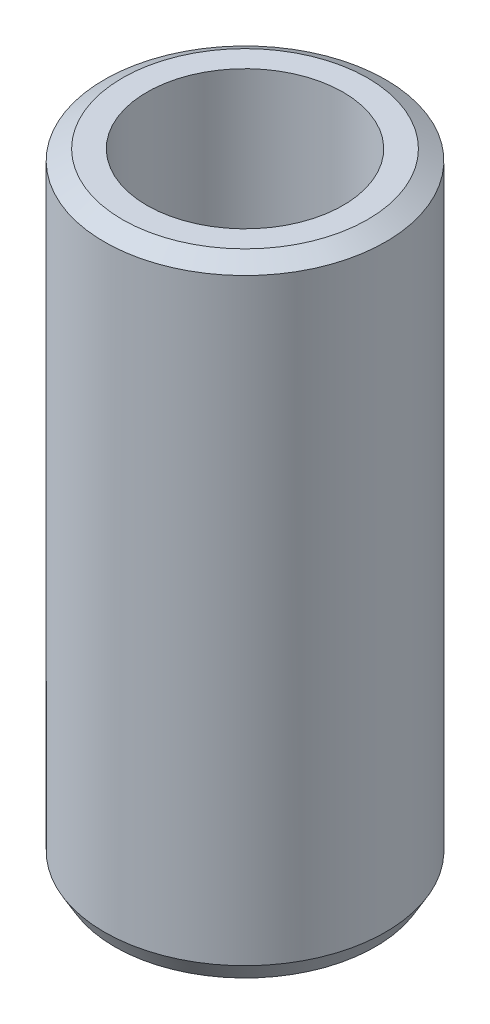
SolidWorks part; units mm, degrees
ref_plane "Front Plane" through (0, 0, 0) normal (0, 0, 1) x (1, 0, 0)
ref_plane "Top Plane" through (0, 0, 0) normal (0, 1, 0) x (1, 0, 0)
ref_plane "Right Plane" through (0, 0, 0) normal (1, 0, 0) x (0, 0, -1)
sketch "Sketch1" plane through (0, 0, 0) normal (0, 1, 0) x (1, 0, 0)
  circle A0 centre (0, 0) radius 55
  dimension "SHAFT_OD" = 110
extrude "Boss-Extrude1" add sketch "Sketch1" along normal blind 244.8653
sketch "Sketch2" plane through (0, 0, 0) normal (0, 1, 0) x (1, 0, 0)
  circle A0 centre (0, 0) radius 38.3686
  dimension "BORE_D" = 76.7371
extrude "Cut-Extrude1" cut sketch "Sketch2" along normal through all
chamfer "Chamfer1" distance 4.0609 angle 60 2 edges at (0, 244.8653, 55) (0, 0, 55) first distance on face at (0, 244.8653, 55) first distance on face at (0, 0, 38.3686)
